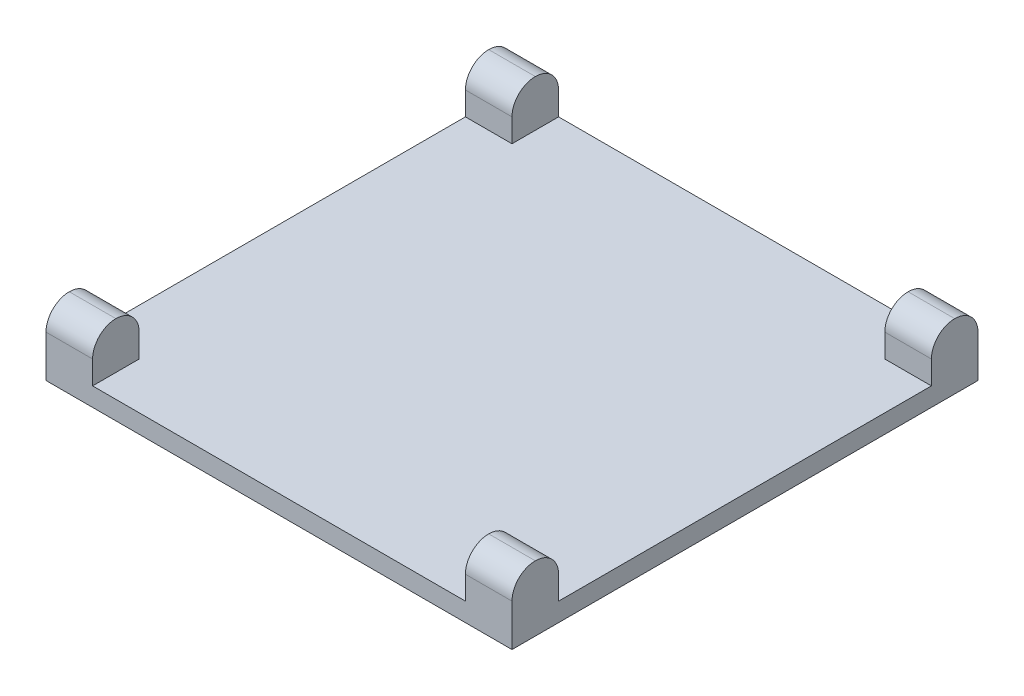
SolidWorks part; units mm, degrees
ref_plane "Front Plane" through (0, 0, 0) normal (0, 0, 1) x (1, 0, 0)
ref_plane "Top Plane" through (0, 0, 0) normal (0, 1, 0) x (1, 0, 0)
ref_plane "Right Plane" through (0, 0, 0) normal (1, 0, 0) x (0, 0, -1)
sketch "Sketch1" plane through (0, 0, 0) normal (0, 1, 0) x (1, 0, 0)
  line L1 (0, 0) -> (63.5, 0)
  line L2 (0, 0) -> (0, 63.5)
  line L3 (0, 63.5) -> (63.5, 63.5)
  line L4 (63.5, 0) -> (63.5, 63.5)
  dimension "D1" = 63.5
  dimension "D2" = 63.5
extrude "Boss-Extrude1" add sketch "Sketch1" along normal blind 2.54
sketch "Sketch2" plane through (0, 2.54, 0) normal (0, 1, 0) x (1, 0, 0)
  line L1 (0, 0) -> (6.35, 0)
  line L2 (0, 0) -> (0, 6.35)
  line L3 (0, 6.35) -> (6.35, 6.35)
  line L4 (6.35, 0) -> (6.35, 6.35)
  line L5 (63.5, 0) -> (57.15, 0)
  line L6 (63.5, 0) -> (63.5, 6.35)
  line L7 (63.5, 6.35) -> (57.15, 6.35)
  line L8 (57.15, 0) -> (57.15, 6.35)
  line L9 (0, 63.5) -> (6.35, 63.5)
  line L10 (0, 63.5) -> (0, 57.15)
  line L11 (0, 57.15) -> (6.35, 57.15)
  line L12 (6.35, 63.5) -> (6.35, 57.15)
  line L13 (63.5, 63.5) -> (57.15, 63.5)
  line L14 (63.5, 63.5) -> (63.5, 57.15)
  line L15 (63.5, 57.15) -> (57.15, 57.15)
  line L16 (57.15, 63.5) -> (57.15, 57.15)
  dimension "D1" = 6.35
  dimension "D2" = 6.35
  dimension "D3" = 6.35
  dimension "D4" = 6.35
  dimension "D5" = 6.35
  dimension "D6" = 6.35
  dimension "D7" = 6.35
  dimension "D8" = 6.35
extrude "Boss-Extrude2" add sketch "Sketch2" along normal blind 6.35
fillet "Fillet1" radius 3.175 8 edges at (3.175, 8.89, -6.35) (3.175, 8.89, 0) (60.325, 8.89, 0) (60.325, 8.89, -6.35) (60.325, 8.89, -63.5) (60.325, 8.89, -57.15) (3.175, 8.89, -63.5) (3.175, 8.89, -57.15)
